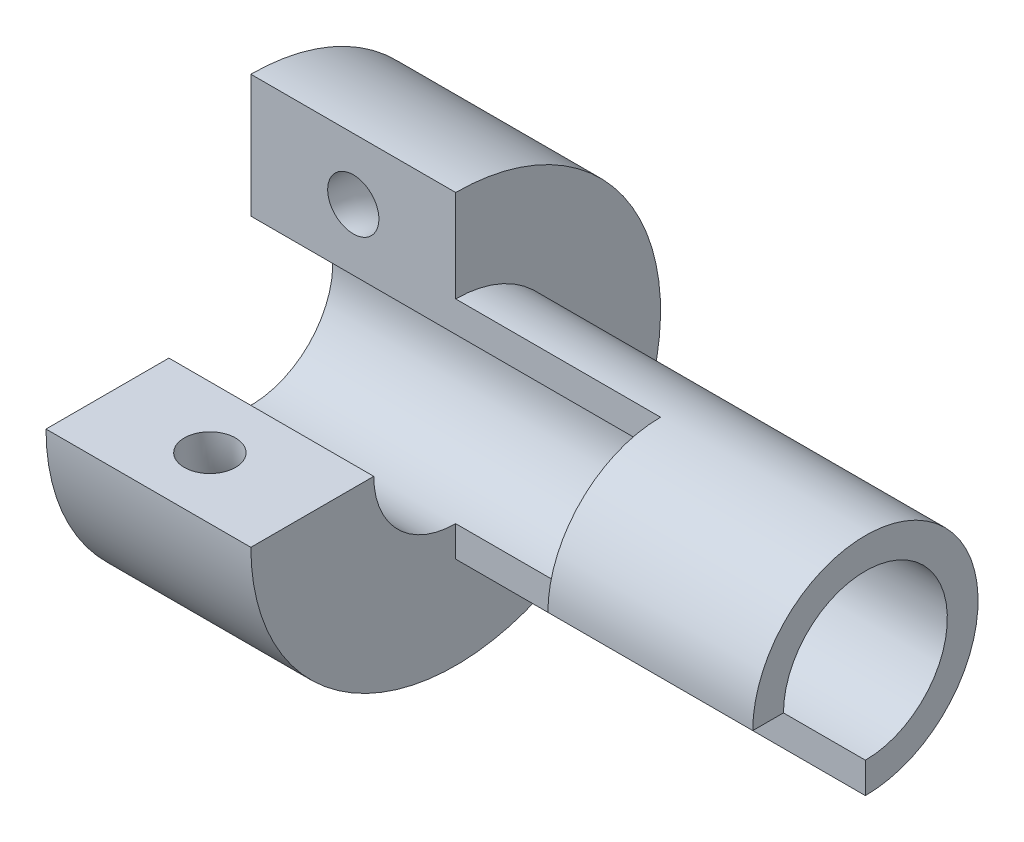
SolidWorks part; units mm, degrees
ref_plane "Front Plane" through (0, 0, 0) normal (0, 0, 1) x (1, 0, 0)
ref_plane "Top Plane" through (0, 0, 0) normal (0, 1, 0) x (1, 0, 0)
ref_plane "Right Plane" through (0, 0, 0) normal (1, 0, 0) x (0, 0, -1)
sketch "Sketch1" plane through (0, 0, 0) normal (1, 0, 0) x (0, 0, -1)
  circle A0 centre (0, 0) radius 11
  circle A1 centre (0, 0) radius 8
  circle A2 centre (0, 0) radius 20
  circle A3 centre (0, 0) radius 14
  dimension "D1" = 22
  dimension "D2" = 16
  dimension "D3" = 40
  dimension "D4" = 28
extrude "Boss-Extrude1" add sketch "Sketch1" against normal blind 20 contours A0 A1 | A1 | A2 region at (0, 0, 10.6889) region at (0, 0, 0)
extrude "Boss-Extrude2" add sketch "Sketch1<4>" along normal blind 40 separate body contours A0 A1 region at (0, 0, 10.6889)
sketch "Sketch1<4>" plane through (0, 0, 0) normal (1, 0, 0) x (0, 0, -1) same geometry as "Sketch1"
sketch "Sketch4" plane through (0, 0, 0) normal (1, 0, 0) x (0, 0, -1)
  line L0 (-11, 0) -> (-8, 0)
  line L1 (0, -8) -> (0, -11)
  arc A0 (-11, 0) -> (0, -11) centre (0, 0) ccw
  circle A1 centre (0, 0) radius 11 construction
  arc A2 (-8, 0) -> (0, -8) centre (0, 0) ccw
  circle A3 centre (0, 0) radius 8 construction
  circle A4 centre (0, 0) radius 11 construction
  point P10 (0, 0)
extrude "Cut-Extrude5" cut sketch "Sketch4" along normal blind 40
extrude "Boss-Extrude3" add sketch "Sketch1<5>" against normal blind 20 contours A0 A1 region at (0, 0, 10.6889)
sketch "Sketch1<5>" plane through (0, 0, 0) normal (1, 0, 0) x (0, 0, -1) same geometry as "Sketch1"
sketch "Sketch6" plane through (0, 0, 0) normal (1, 0, 0) x (0, 0, -1)
  line L0 (0, 20) -> (0, 11)
  line L1 (-20, 0) -> (-11, 0)
  arc A1 (-20, 0) -> (0, 20) centre (0, 0) cw
  circle A2 centre (0, 0) radius 20 construction
  arc A3 (0, -11) -> (-11, 0) centre (0, 0) ccw construction
  arc A4 (-11, 0) -> (0, 11) centre (0, 0) cw
  circle M5 centre (0, 0) radius 20
  arc M6 (-11, 0) -> (0, -11) centre (0, 0) cw
extrude "Cut-Extrude7" cut sketch "Sketch6" against normal blind 20 contours L1 L0 M5 M6 region at (0, 10.1448, 10.1448)
sketch "Sketch7" plane through (0, 0, 0) normal (1, 0, 0) x (0, 0, -1)
  line L0 (-8, 0) -> (-11, 0) construction
  line L1 (-11, 0) -> (-8, 0)
  line L2 (0, 8) -> (0, 11)
  arc A0 (0, 8) -> (-8, 0) centre (0, 0) ccw
  arc A1 (0, -8) -> (-8, 0) centre (0, 0) ccw construction
  arc A2 (0, 11) -> (-11, 0) centre (0, 0) ccw
  arc A3 (0, -11) -> (-11, 0) centre (0, 0) ccw construction
  point P14 (0, 0)
extrude "Cut-Extrude8" cut sketch "Sketch7" against normal blind 20 and the other way blind 20
sketch "Sketch8" plane through (0, 0, 0) normal (0, 0, 1) x (1, 0, 0)
  line L0 (-20, 20) -> (-20, 8) construction
  line L1 (-20, 20) -> (0, 20) construction
  circle A0 centre (-10, 14) radius 2.5
  dimension "D1" = 5
  dimension "D2" = 10
  dimension "D3" = 6
sketch "Sketch9" plane through (0, 0, 0) normal (0, 1, 0) x (1, 0, 0)
  point P2 (0, 0)
ref_plane "Plane1" through (-10, 0, 0) normal (-1, 0, 0) x (0, 0, 1)
sketch "Sketch10" plane through (-10, 0, 0) normal (-1, 0, 0) x (0, 0, 1)
  circle A0 centre (0, 0) radius 14
  dimension "D1" = 28
sweep "Cut-Sweep1" cut profiles "Sketch8" path "Sketch10"
